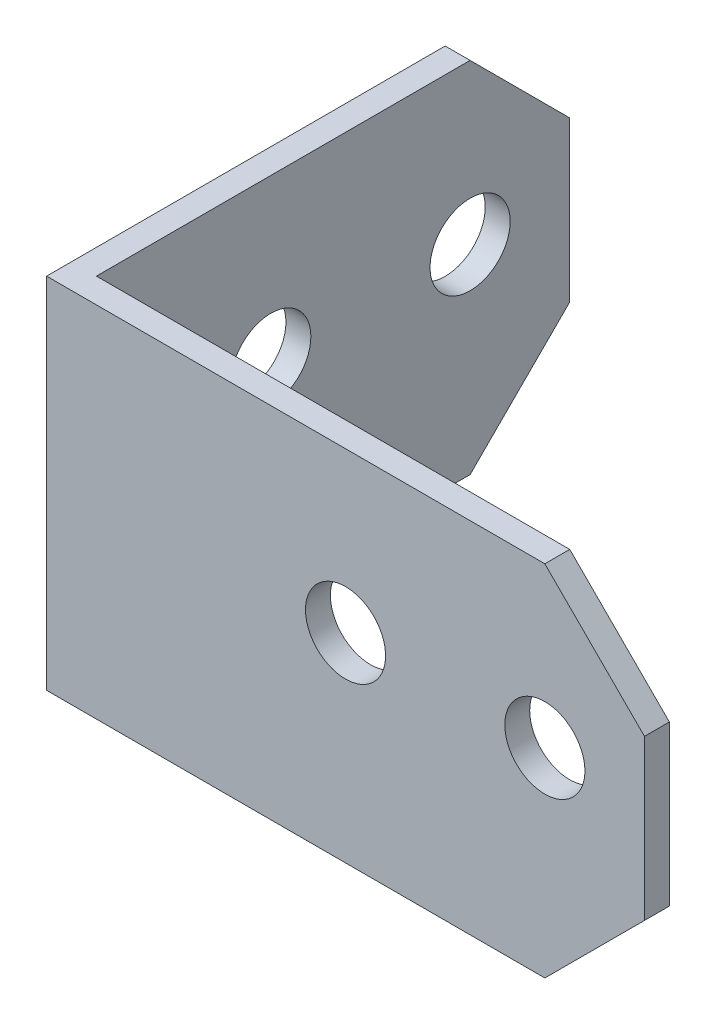
SolidWorks part; units mm, degrees
material "6061-T6 (SS)"
ref_plane "Front Plane" through (0, 0, 0) normal (0, 0, 1) x (1, 0, 0)
ref_plane "Top Plane" through (0, 0, 0) normal (0, 1, 0) x (1, 0, 0)
ref_plane "Right Plane" through (0, 0, 0) normal (1, 0, 0) x (0, 0, -1)
sketch "Sketch1" plane through (0, 0, 0) normal (0, 1, 0) x (1, 0, 0)
  line L1 (-18.1093, 25.3412) -> (-16.5218, 25.3412)
  line L2 (-18.1093, 25.3412) -> (-18.1093, -6.4088)
  line L4 (-16.5218, 25.3412) -> (-16.5218, -4.8213)
  line L5 (-18.1093, -6.4088) -> (19.9907, -6.4088)
  line L7 (-16.5218, -4.8213) -> (19.9907, -4.8213)
  line L8 (19.9907, -6.4088) -> (19.9907, -4.8213)
  dimension "D1" = 1.5875
  dimension "D2" = 1.5875
  dimension "D3" = 31.75
  dimension "D4" = 38.1
extrude "Boss-Extrude1" add sketch "Sketch1" along normal blind 45.72 contours L2 L5 L8 L7 L4 L1
sketch "Sketch2" plane through (0, 0, 4.8213) normal (0, 0, -1) x (-1, 0, 0)
  line L1 (-13.6407, 35.56) -> (-0.9407, 35.56) construction
  line L2 (-13.6407, 35.56) -> (-13.6407, 10.16) construction
  line L3 (-13.6407, 10.16) -> (-0.9407, 10.16) construction
  line L4 (-0.9407, 35.56) -> (-0.9407, 10.16) construction
  line L5 (18.1093, 45.72) -> (18.1093, 0) construction
  line L6 (16.5218, 45.72) -> (-19.9907, 45.72) construction
  circle A0 centre (-0.9407, 35.56) radius 2.5527
  circle A1 centre (-13.6407, 35.56) radius 2.5527
  circle A2 centre (-13.6407, 10.16) radius 2.5527
  circle A3 centre (-0.9407, 10.16) radius 2.5527
  dimension "D5" = 5.1054
  dimension "D1" = 12.7
  dimension "D2" = 19.05
  dimension "D3" = 10.16
  dimension "D4" = 25.4
extrude "Cut-Extrude1" cut sketch "Sketch2" against normal through all
sketch "Sketch3" plane through (-16.5218, 0, 0) normal (1, 0, 0) x (0, 0, -1)
  line L0 (-6.4088, 45.72) -> (-6.4088, 0) construction
  line L1 (18.9912, 35.56) -> (6.2912, 35.56) construction
  line L2 (18.9912, 35.56) -> (18.9912, 10.16) construction
  line L3 (18.9912, 10.16) -> (6.2912, 10.16) construction
  line L4 (6.2912, 35.56) -> (6.2912, 10.16) construction
  line L5 (25.3412, 45.72) -> (-4.8213, 45.72) construction
  circle A0 centre (6.2912, 35.56) radius 2.5527
  circle A1 centre (18.9912, 35.56) radius 2.5527
  circle A2 centre (18.9912, 10.16) radius 2.5527
  circle A3 centre (6.2912, 10.16) radius 2.5527
  dimension "D5" = 5.1054
  dimension "D1" = 12.7
  dimension "D2" = 25.4
  dimension "D3" = 10.16
  dimension "D4" = 12.7
extrude "Cut-Extrude2" cut sketch "Sketch3" against normal through all
chamfer "Chamfer1" distance 6.35 angle 45 4 edges at (19.9907, 45.72, 5.615) (19.9907, 0, 5.615) (-17.3155, 0, -25.3412) (-17.3155, 45.72, -25.3412)
sketch "Sketch4" plane through (0, 0, 4.8213) normal (0, 0, -1) x (-1, 0, 0)
  line L0 (-19.9907, 22.86) -> (16.5218, 22.86)
  line L1 (-19.9907, 39.37) -> (-19.9907, 6.35) construction
  line L2 (16.5218, 45.72) -> (16.5218, 0) construction
  line L3 (16.5218, 22.86) -> (16.5218, 0)
  line L4 (16.5218, 0) -> (-13.6407, 0)
  line L5 (-13.6407, 0) -> (-19.9907, 6.35)
  line L6 (-19.9907, 6.35) -> (-19.9907, 22.86)
sketch "Sketch5" plane through (-16.5218, 0, 0) normal (1, 0, 0) x (0, 0, -1)
  line L0 (25.3412, 22.86) -> (-4.8213, 22.86)
  line L1 (25.3412, 39.37) -> (25.3412, 6.35) construction
  line L2 (-4.8213, 22.86) -> (-4.8213, 0)
  line L3 (-4.8213, 0) -> (18.9912, 0)
  line L4 (18.9912, 0) -> (25.3412, 6.35)
  line L5 (25.3412, 6.35) -> (25.3412, 22.86)
extrude "Cut-Extrude3" cut sketch "Sketch4" against normal through all
extrude "Cut-Extrude4" cut sketch "Sketch5" against normal through all
sketch "Sketch6" plane through (0, 0, 6.4088) normal (0, 0, 1) x (1, 0, 0)
  line L0 (-18.1093, 45.72) -> (-18.1093, 0) construction
  line L1 (-18.1093, 22.86) -> (-16.5218, 22.86)
  line L2 (-18.1093, 22.86) -> (-18.1093, 0)
  line L3 (-18.1093, 0) -> (-16.5218, 0)
  line L4 (-16.5218, 22.86) -> (-16.5218, 0)
extrude "Cut-Extrude5" cut sketch "Sketch6" against normal through all
chamfer "Chamfer2" distance 6.35 angle 45 2 edges at (-17.3155, 22.86, -25.3412) (19.9907, 22.86, 5.615)
